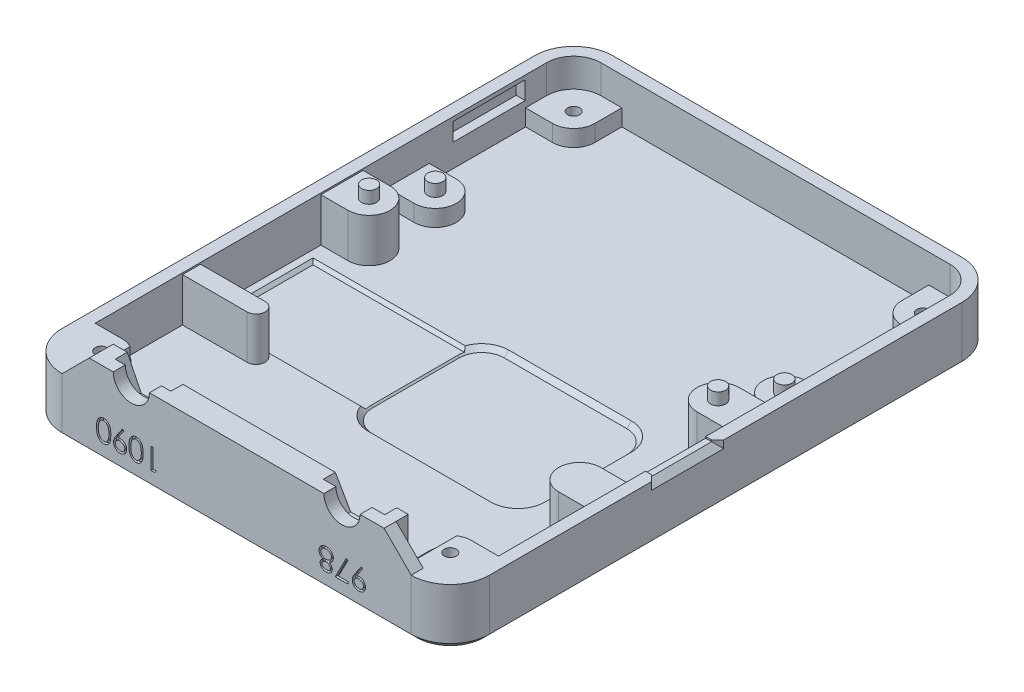
SolidWorks part; units mm, degrees
ref_plane "Front Plane" through (0, 0, 0) normal (0, 0, 1) x (1, 0, 0)
ref_plane "Top Plane" through (0, 0, 0) normal (0, 1, 0) x (1, 0, 0)
ref_plane "Right Plane" through (0, 0, 0) normal (1, 0, 0) x (0, 0, -1)
sketch "Sketch1" plane through (0, 0, 0) normal (0, 1, 0) x (1, 0, 0)
  line L0 (-33.8462, -25.5532) -> (31.1538, -25.5532)
  line L1 (-33.8462, 38.4468) -> (31.1538, 38.4468)
  line L2 (-33.8462, 38.4468) -> (-33.8462, 8.4468)
  line L3 (-33.8462, 8.4468) -> (31.1538, 8.4468)
  line L4 (31.1538, 38.4468) -> (31.1538, 8.4468)
  line L5 (-30.3462, 34.9468) -> (27.6538, 34.9468)
  line L6 (-30.3462, 34.9468) -> (-30.3462, 11.9468)
  line L7 (-30.3462, 11.9468) -> (27.6538, 11.9468)
  line L8 (27.6538, 34.9468) -> (27.6538, 11.9468)
  line L9 (-30.3462, 0.9468) -> (27.6538, 0.9468)
  line L10 (-30.3462, 0.9468) -> (-30.3462, -22.0532)
  line L11 (-33.8462, 4.4468) -> (31.1538, 4.4468)
  line L12 (-33.8462, 4.4468) -> (-33.8462, -25.5532)
  line L13 (-30.3462, -22.0532) -> (27.6538, -22.0532)
  line L14 (31.1538, 4.4468) -> (31.1538, -25.5532)
  line L15 (27.6538, 0.9468) -> (27.6538, -22.0532)
  line L16 (-37.9161, 25.3468) -> (-35.3276, 25.3468)
  line L17 (7.5538, 7.5472) -> (7.5538, 6.2645)
  line L18 (20.1538, 7.5472) -> (20.1538, 6.2645)
  dimension "D1" = 65
  dimension "D2" = 30
  dimension "D3" = 58
  dimension "D4" = 23
  dimension "D5" = 3.5
  dimension "D6" = 3.5
  dimension "D7" = 65
  dimension "D8" = 30
  dimension "D9" = 58
  dimension "D10" = 23
  dimension "D11" = 3.5
  dimension "D12" = 3.5
  dimension "D13" = 4
  dimension "D14" = 16.9
  dimension "D15" = 41.4
  dimension "D16" = 54
sketch "Sketch2" plane through (0, 0, 0) normal (0, 1, 0) x (1, 0, 0)
  line L0 (-33.8462, 38.4468) -> (-33.8462, 8.4468) construction
  line L1 (-30.3462, 39.4468) -> (27.6538, 39.4468)
  line L2 (-34.8462, 34.9468) -> (-34.8462, -43.5532)
  line L3 (-30.3462, -48.0532) -> (27.6538, -48.0532)
  line L4 (32.1538, 34.9468) -> (32.1538, -43.5532)
  line L5 (-33.8462, 38.4468) -> (31.1538, 38.4468) construction
  line L6 (31.1538, 38.4468) -> (31.1538, 8.4468) construction
  line L7 (-30.3462, 41.4468) -> (27.6538, 41.4468)
  line L8 (34.1538, 34.9468) -> (34.1538, -43.5532)
  line L9 (-30.3462, -50.0532) -> (27.6538, -50.0532)
  line L10 (-36.8462, 34.9468) -> (-36.8462, -43.5532)
  line L11 (-34.8462, 39.4468) -> (32.1538, 39.4468) construction
  line L12 (-34.8462, 39.4468) -> (-34.8462, -48.0532) construction
  line L13 (-36.8462, 41.4468) -> (-36.8462, -50.0532) construction
  line L14 (-36.8462, 41.4468) -> (34.1538, 41.4468) construction
  line L15 (32.1538, 39.4468) -> (32.1538, -48.0532) construction
  line L16 (34.1538, 41.4468) -> (34.1538, -50.0532) construction
  line L17 (-36.8462, -50.0532) -> (34.1538, -50.0532) construction
  line L18 (-34.8462, -48.0532) -> (32.1538, -48.0532) construction
  arc A0 (-30.3462, 39.4468) -> (-34.8462, 34.9468) centre (-30.3462, 34.9468) ccw
  arc A1 (-36.8462, 34.9468) -> (-30.3462, 41.4468) centre (-30.3462, 34.9468) cw
  arc A2 (32.1538, 34.9468) -> (27.6538, 39.4468) centre (27.6538, 34.9468) ccw
  arc A3 (34.1538, 34.9468) -> (27.6538, 41.4468) centre (27.6538, 34.9468) ccw
  arc A4 (27.6538, -50.0532) -> (34.1538, -43.5532) centre (27.6538, -43.5532) ccw
  arc A5 (-36.8462, -43.5532) -> (-30.3462, -50.0532) centre (-30.3462, -43.5532) ccw
  arc A6 (27.6538, -48.0532) -> (32.1538, -43.5532) centre (27.6538, -43.5532) ccw
  arc A7 (-30.3462, -48.0532) -> (-34.8462, -43.5532) centre (-30.3462, -43.5532) cw
  dimension "D6" = 4.5
  dimension "D7" = 6.5
  dimension "D8" = 4.5
  dimension "D9" = 6.5
  dimension "D10" = 6.5
  dimension "D11" = 4.5
  dimension "D1" = 1
  dimension "D2" = 1
  dimension "D3" = 1
  dimension "D4" = 87.5
  dimension "D5" = 2
extrude "Boss-Extrude1" add sketch "Sketch2" along normal blind 9.5
sketch "Sketch3" plane through (0, 0, 0) normal (0, 1, 0) x (1, 0, 0)
  line L0 (-30.3462, -48.0532) -> (27.6538, -48.0532)
  line L1 (-30.3462, 39.4468) -> (27.6538, 39.4468)
  line L2 (-34.8462, 34.9468) -> (-34.8462, -43.5532)
  line L4 (32.1538, 34.9468) -> (32.1538, -43.5532)
  arc A0 (-34.8462, -43.5532) -> (-30.3462, -48.0532) centre (-30.3462, -43.5532) ccw
  arc A1 (27.6538, -48.0532) -> (32.1538, -43.5532) centre (27.6538, -43.5532) ccw
  arc A2 (32.1538, 34.9468) -> (27.6538, 39.4468) centre (27.6538, 34.9468) ccw
  arc A3 (-30.3462, 39.4468) -> (-34.8462, 34.9468) centre (-30.3462, 34.9468) ccw
  point P15 (-34.8462, 39.4468)
  dimension "D1" = 4.5
  dimension "D2" = 4.5
  dimension "D3" = 87.5
extrude "Boss-Extrude2" add sketch "Sketch3" along normal blind 2
sketch "Sketch4" plane through (0, 2, 0) normal (0, 1, 0) x (1, 0, 0)
  line L1 (-4.1234, -3.5548) -> (16.2444, -3.5548)
  line L2 (-7.1234, -6.5548) -> (-7.1234, -20.9191)
  line L3 (-4.1234, -23.9191) -> (16.2444, -23.9191)
  line L4 (19.2444, -6.5548) -> (19.2444, -20.9191)
  arc A0 (16.2444, -23.9191) -> (19.2444, -20.9191) centre (16.2444, -20.9191) ccw
  arc A1 (-7.1234, -20.9191) -> (-4.1234, -23.9191) centre (-4.1234, -20.9191) ccw
  arc A2 (19.2444, -6.5548) -> (16.2444, -3.5548) centre (16.2444, -6.5548) ccw
  arc A3 (-7.1234, -6.5548) -> (-4.1234, -3.5548) centre (-4.1234, -6.5548) cw
  dimension "D1" = 3
extrude "Cut-Extrude2" cut sketch "Sketch4" against normal blind 0.75
chamfer "Chamfer1" distance 1.5 angle 45 8 edges at (6.0605, 2, 23.9191) (18.3657, 2, 23.0404) (-6.2447, 2, 23.0404) (19.2444, 2, 13.7369) (-7.1234, 2, 13.7369) (18.3657, 2, 4.4335) (-6.2447, 2, 4.4335) (6.0605, 2, 3.5548) tangent propagation no
sketch "Sketch5" plane through (0, 1.25, 0) normal (0, 1, 0) x (1, 0, 0)
  line L0 (-30.3462, 4.4468) -> (-34.8462, 4.4468)
  line L1 (-34.8462, 34.9468) -> (-34.8462, -43.5532) construction
  line L2 (-34.8462, 4.4468) -> (-34.8462, -2.5532)
  line L3 (-34.8462, -2.5532) -> (-30.3462, -2.5532)
  line L4 (27.6538, 4.4468) -> (32.1538, 4.4468)
  line L5 (32.1538, -43.5532) -> (32.1538, 34.9468) construction
  line L6 (32.1538, 4.4468) -> (32.1538, -2.5532)
  line L7 (32.1538, -43.5532) -> (32.1538, 34.9468) construction
  line L8 (32.1538, -2.5532) -> (27.6538, -2.5532)
  line L9 (32.1538, -18.5532) -> (32.1538, -25.5532)
  line L10 (-34.8462, -25.5532) -> (-24.1094, -25.5532)
  line L11 (-34.8462, -25.5532) -> (-34.8462, -22.5532)
  line L12 (-34.8462, -22.5532) -> (-24.1094, -22.5532)
  line L13 (32.1538, -25.5532) -> (27.6538, -25.5532)
  line L14 (27.6538, -18.5532) -> (32.1538, -18.5532)
  arc A0 (-30.3462, -2.5532) -> (-30.3462, 4.4468) centre (-30.3462, 0.9468) ccw
  arc A1 (27.6538, 4.4468) -> (27.6538, -2.5532) centre (27.6538, 0.9468) ccw
  arc A2 (-24.1094, -22.5532) -> (-24.1094, -25.5532) centre (-24.1094, -24.0532) cw
  arc A3 (27.6538, -18.5532) -> (27.6538, -25.5532) centre (27.6538, -22.0532) ccw
  dimension "D1" = 3
extrude "Boss-Extrude3" add sketch "Sketch5" along normal blind 8
sketch "Sketch6" plane through (0, 1.25, 0) normal (0, 1, 0) x (1, 0, 0)
  line L0 (-30.3462, 15.4468) -> (-34.8462, 15.4468)
  line L1 (-34.8462, 34.9468) -> (-34.8462, -43.5532) construction
  line L2 (-34.8462, 15.4468) -> (-34.8462, 8.4468)
  line L3 (-34.8462, 34.9468) -> (-34.8462, 4.4468) construction
  line L4 (-34.8462, 8.4468) -> (-30.3462, 8.4468)
  line L5 (-26.8462, 34.9468) -> (-26.8462, 39.4468)
  line L6 (27.6538, 39.4468) -> (-30.3462, 39.4468) construction
  line L7 (-26.8462, 39.4468) -> (-30.3462, 39.4468)
  line L8 (-30.3462, 31.4468) -> (-34.8462, 31.4468)
  line L9 (-34.8462, 31.4468) -> (-34.8462, 34.9468)
  line L10 (24.1538, 34.9468) -> (24.1538, 39.4468)
  line L11 (24.1538, 39.4468) -> (27.6538, 39.4468)
  line L12 (27.6538, 31.4468) -> (32.1538, 31.4468)
  line L13 (32.1538, 4.4468) -> (32.1538, 34.9468) construction
  line L14 (32.1538, 31.4468) -> (32.1538, 34.9468)
  line L15 (27.6538, 15.4468) -> (32.1538, 15.4468)
  line L16 (27.6538, 8.4468) -> (32.1538, 8.4468)
  line L17 (32.1538, -43.5532) -> (32.1538, 34.9468) construction
  line L18 (32.1538, 8.4468) -> (32.1538, 15.4468)
  arc A0 (-30.3462, 31.4468) -> (-26.8462, 34.9468) centre (-30.3462, 34.9468) ccw
  arc A1 (24.1538, 34.9468) -> (27.6538, 31.4468) centre (27.6538, 34.9468) ccw
  arc A2 (27.6538, 15.4468) -> (27.6538, 8.4468) centre (27.6538, 11.9468) ccw
  arc A3 (-30.3462, 8.4468) -> (-30.3462, 15.4468) centre (-30.3462, 11.9468) ccw
  arc A4 (-30.3462, 39.4468) -> (-34.8462, 34.9468) centre (-30.3462, 34.9468) ccw
  arc A5 (32.1538, 34.9468) -> (27.6538, 39.4468) centre (27.6538, 34.9468) ccw
  dimension "D1" = 4.5
  dimension "D2" = 4.5
extrude "Boss-Extrude4" add sketch "Sketch6" along normal blind 3.5
sketch "Sketch7" plane through (0, 0, 50.0532) normal (0, 0, 1) x (1, 0, 0)
  line L0 (27.6538, 9.5) -> (-30.3462, 9.5)
  line L3 (13.1538, 14) -> (-15.8462, 14)
  line L4 (-1.3462, 9.5) -> (-1.3462, 14) construction
  line L5 (-30.3462, 9.5) -> (27.6538, 9.5) construction
  line L6 (-30.3462, 9.5) -> (-25.8462, 14)
  line L7 (-25.8462, 14) -> (-21.8462, 14)
  line L9 (23.1538, 14) -> (19.1538, 14)
  line L13 (27.6538, 9.5) -> (23.1538, 14)
  arc A0 (-21.8462, 14) -> (-15.8462, 14) centre (-18.8462, 14) ccw
  arc A1 (13.1538, 14) -> (19.1538, 14) centre (16.1538, 14) ccw
  dimension "D2" = 35
  dimension "D1" = 4.5
  dimension "D6" = 3
  dimension "D7" = 3
  dimension "D3" = 4.5
  dimension "D4" = 45
  dimension "D5" = 4.5
extrude "Boss-Extrude5" add sketch "Sketch7" against normal up to vertex (2 mm away) up to point (-30.3462, 9.5, 48.0532)
sketch "Sketch10" plane through (0, 2, 0) normal (0, 1, 0) x (1, 0, 0)
  line L0 (-30.3462, -40.0532) -> (-34.8462, -40.0532)
  line L1 (27.6538, -40.0532) -> (32.1538, -40.0532)
  line L2 (-34.8462, -40.0532) -> (-34.8462, -43.5532)
  line L3 (-26.8462, -43.5532) -> (-26.8462, -48.0532)
  line L4 (32.1538, -43.5532) -> (32.1538, 34.9468) construction
  line L5 (-26.8462, -48.0532) -> (-30.3462, -48.0532)
  line L6 (32.1538, -40.0532) -> (32.1538, -43.5532)
  line L7 (24.1538, -43.5532) -> (24.1538, -48.0532)
  line L8 (-30.3462, -48.0532) -> (27.6538, -48.0532) construction
  line L9 (24.1538, -48.0532) -> (27.6538, -48.0532)
  arc A0 (-34.8462, -43.5532) -> (-30.3462, -48.0532) centre (-30.3462, -43.5532) ccw
  arc A1 (-26.8462, -43.5532) -> (-30.3462, -40.0532) centre (-30.3462, -43.5532) ccw
  arc A2 (32.1538, -43.5532) -> (27.6538, -48.0532) centre (27.6538, -43.5532) cw
  arc A3 (27.6538, -48.0532) -> (32.1538, -43.5532) centre (27.6538, -43.5532) ccw construction
  arc A4 (27.6538, -40.0532) -> (24.1538, -43.5532) centre (27.6538, -43.5532) ccw
extrude "Boss-Extrude6" add sketch "Sketch10" along normal up to vertex (7.5 mm away) up to point (-34.8462, 9.5, 43.5532)
sketch "Sketch11" plane through (34.1538, 0, 0) normal (1, 0, 0) x (0, 0, -1)
  line L1 (-15.6251, 10.2426) -> (-5.6251, 10.2426)
  line L2 (-15.6251, 10.2426) -> (-15.6251, 9.2424)
  line L3 (-15.6251, 9.2424) -> (-5.6251, 9.2424)
  line L4 (-5.6251, 10.2426) -> (-5.6251, 9.2424)
extrude "Cut-Extrude3" cut sketch "Sketch11" against normal up to next
chamfer "Chamfer2" distance 1 angle 45 3 edges at (34.1538, 9.3712, 5.6251) (34.1538, 9.3712, 15.6251) (34.1538, 9.2424, 10.6251)
sketch "Sketch12" plane through (-34.8462, 0, 0) normal (-1, 0, 0) x (0, 0, 1)
  line L1 (-31.3918, 8.8223) -> (-19.3918, 8.8223)
  line L2 (-31.3918, 8.8223) -> (-31.3918, 5.8223)
  line L3 (-31.3918, 5.8223) -> (-19.3918, 5.8223)
  line L4 (-19.3918, 8.8223) -> (-19.3918, 5.8223)
  line L5 (-31.3918, 8.8223) -> (-19.3918, 5.8223) construction
  line L6 (-31.3918, 5.8223) -> (-19.3918, 8.8223) construction
  point P0 (-25.3918, 7.3223)
  dimension "D1" = 12
  dimension "D2" = 3
chamfer "Chamfer4" distance 1 angle 45 8 edges at (34.1538, 0, 4.3032) (32.25, 0, -39.543) (32.25, 0, 48.1493) (-1.3462, 0, -41.4468) (-1.3462, 0, 50.0532) (-34.9423, 0, -39.543) (-34.9423, 0, 48.1493) (-36.8462, 0, 4.3032)
hole_wizard "Ø2.0 (2) Diameter Hole1" positions "Sketch14" profile "Sketch13" hole size "Ø2.0" standard "ANSI Metric" end condition through all
sketch "Sketch14" plane through (0, 0, 0) normal (0, -1, 0) x (-1, 0, 0)
  point P0 (30.3462, -43.5532)
sketch "Sketch13" plane through (-30.3462, 0, 43.5532) normal (1, 0, 0) x (0, 0, -1)
  line L0 (0, 0) -> (0, 14)
  line L1 (0, 14) -> (1, 14)
  line L2 (1, 14) -> (1, 0)
  line L5 (1, 0) -> (0, 0)
  line L11 (0, -6.35) -> (0, 107.95) construction
  dimension "Thru Hole Dia." = 2
  dimension "Thru Hole Depth" = 14
hole_wizard "Ø2.0 (2) Diameter Hole2" positions "Sketch16" profile "Sketch15" hole size "Ø2.0" standard "ANSI Metric" end condition through all
sketch "Sketch16" plane through (0, 0, 0) normal (0, -1, 0) x (-1, 0, 0)
  point P0 (-27.6538, -43.5532)
sketch "Sketch15" plane through (27.6538, 0, 43.5532) normal (1, 0, 0) x (0, 0, -1)
  line L0 (0, 0) -> (0, 14)
  line L1 (0, 14) -> (1, 14)
  line L2 (1, 14) -> (1, 0)
  line L5 (1, 0) -> (0, 0)
  line L11 (0, -6.35) -> (0, 107.95) construction
  dimension "Thru Hole Dia." = 2
  dimension "Thru Hole Depth" = 14
hole_wizard "Ø2.0 (2) Diameter Hole3" positions "Sketch18" profile "Sketch17" hole size "Ø2.0" standard "ANSI Metric" end condition through all
sketch "Sketch18" plane through (0, 0, 0) normal (0, -1, 0) x (-1, 0, 0)
  point P0 (30.3462, 34.9468)
sketch "Sketch17" plane through (-30.3462, 0, -34.9468) normal (1, 0, 0) x (0, 0, -1)
  line L0 (0, 0) -> (0, 14)
  line L1 (0, 14) -> (1, 14)
  line L2 (1, 14) -> (1, 0)
  line L5 (1, 0) -> (0, 0)
  line L11 (0, -6.35) -> (0, 107.95) construction
  dimension "Thru Hole Dia." = 2
  dimension "Thru Hole Depth" = 14
hole_wizard "Ø2.0 (2) Diameter Hole4" positions "Sketch20" profile "Sketch19" hole size "Ø2.0" standard "ANSI Metric" end condition through all
sketch "Sketch20" plane through (0, 0, 0) normal (0, -1, 0) x (-1, 0, 0)
  point P0 (-27.6538, 34.9468)
sketch "Sketch19" plane through (27.6538, 0, -34.9468) normal (1, 0, 0) x (0, 0, -1)
  line L0 (0, 0) -> (0, 14)
  line L1 (0, 14) -> (1, 14)
  line L2 (1, 14) -> (1, 0)
  line L5 (1, 0) -> (0, 0)
  line L11 (0, -6.35) -> (0, 107.95) construction
  dimension "Thru Hole Dia." = 2
  dimension "Thru Hole Depth" = 14
sketch "Sketch34" plane through (0, 2, 0) normal (0, 1, 0) x (1, 0, 0)
  line L1 (-5.843, -6.5548) -> (-32.1578, -6.5548)
  line L2 (-5.843, -6.5548) -> (-5.843, -20.9191)
  line L3 (-5.843, -20.9191) -> (-32.1578, -20.9191)
  line L4 (-32.1578, -6.5548) -> (-32.1578, -20.9191)
extrude "Cut-Extrude5" cut sketch "Sketch34" against normal blind 0.5
chamfer "Chamfer5" distance 1.5 angle 45 3 edges at (-20.3906, 2, 20.9191) (-32.1578, 2, 13.7369) (-20.3906, 2, 6.5548)
extrude "Cut-Extrude6" cut sketch "Sketch12" along normal blind 1.5
sketch "Sketch35" plane through (0, 9.5, 0) normal (0, 1, 0) x (1, 0, 0)
  line L0 (-30.3462, -48.0532) -> (-26.8462, -48.0532) construction
  line L1 (-28.5962, -48.0532) -> (25.7783, -48.0532)
  line L2 (-28.5962, -48.0532) -> (-28.5962, -29.9744)
  line L3 (-28.5962, -29.9744) -> (25.7783, -29.9744)
  line L4 (25.7783, -48.0532) -> (25.7783, -29.9744)
extrude "Cut-Extrude7" cut sketch "Sketch35" against normal blind 1.5
sketch "Sketch36" plane through (0, 0, 0) normal (0, -1, 0) x (1, 0, 0)
  line L0 (-5.6411, -4.4361) -> (-6.5788, -2.9987)
  line L1 (-5.6135, -17.5484) -> (-6.5451, -18.9896)
  line L2 (2.8733, -4.4181) -> (3.8048, -2.9769)
  line L3 (2.9009, -17.5304) -> (3.8385, -18.9678)
  line L4 (-14.7411, -31.67) -> (-15.5841, -32.9742)
  line L5 (-9.464, -23.5056) -> (-10.3585, -24.8894)
  line L6 (-9.5167, 1.5049) -> (-10.4169, 2.885)
  line L7 (-14.8281, 9.647) -> (-15.6766, 10.9477)
  line L8 (12.0008, 9.7035) -> (12.8438, 11.0078)
  line L9 (6.7238, 1.5391) -> (7.6182, 2.9229)
  line L10 (6.7764, -23.4714) -> (7.6767, -24.8515)
  line L11 (12.0878, -31.6135) -> (12.9363, -32.9142)
  line L12 (-3.5903, -40.4468) -> (-2.2438, -13.3244)
  line L13 (0.898, -40.4468) -> (-0.192, -13.3244)
  line L14 (-3.5903, -40.4468) -> (0.898, -40.4468)
  line L15 (-2.2438, -13.3244) -> (-0.192, -13.3244)
  arc A0 (12.9363, -32.9142) -> (12.8438, 11.0078) centre (-1.3701, -10.9832) ccw
  arc A1 (12.0878, -31.6135) -> (12.0008, 9.7035) centre (-1.3701, -10.9832) ccw
  arc A2 (2.9009, -17.5304) -> (2.8733, -4.4181) centre (-1.3701, -10.9832) ccw
  arc A3 (3.8385, -18.9678) -> (3.8048, -2.9769) centre (-1.3701, -10.9832) ccw
  arc A4 (7.6767, -24.8515) -> (7.6182, 2.9229) centre (-1.3701, -10.9832) ccw
  arc A5 (6.7764, -23.4714) -> (6.7238, 1.5391) centre (-1.3701, -10.9832) ccw
  arc A6 (-15.6766, 10.9477) -> (-15.5841, -32.9742) centre (-1.3701, -10.9832) ccw
  arc A7 (-14.8281, 9.647) -> (-14.7411, -31.67) centre (-1.3701, -10.9832) ccw
  arc A8 (-10.4169, 2.885) -> (-10.3585, -24.8894) centre (-1.3701, -10.9832) ccw
  arc A9 (-9.5167, 1.5049) -> (-9.464, -23.5056) centre (-1.3701, -10.9832) ccw
  arc A10 (-6.5788, -2.9987) -> (-6.5451, -18.9896) centre (-1.3701, -10.9832) ccw
  arc A11 (-5.6411, -4.4361) -> (-5.6135, -17.5484) centre (-1.3701, -10.9832) ccw
extrude "Cut-Extrude8" cut sketch "Sketch36" against normal blind 0.4
sketch "Sketch37" plane through (0, 0, 0) normal (0, 1, 0) x (1, 0, 0)
  line L0 (-1.9008, 5.7134) -> (12.3211, -8.0776)
  line L1 (12.3211, -8.0776) -> (16.1409, -4.1385)
  line L2 (16.1409, -4.1385) -> (3.4609, 11.2426)
  line L3 (3.4609, 11.2426) -> (9.8009, 20.3663)
  line L4 (9.8009, 20.3663) -> (15.1149, 16.2462)
  line L5 (15.1149, 16.2462) -> (17.8041, 19.0194)
  line L6 (17.8041, 19.0194) -> (12.774, 24.201)
  line L7 (12.774, 24.201) -> (13.7731, 25.4896)
  line L8 (13.7731, 25.4896) -> (13.4862, 25.712)
  line L9 (-1.9008, 5.7134) -> (-4.5225, 3.5521)
  line L10 (-4.5225, 3.5521) -> (-6.7547, 2.0307)
  line L11 (-6.7547, 2.0307) -> (-8.3897, 1.1526)
  line L12 (-8.3897, 1.1526) -> (-9.0215, 1.5916)
  line L13 (-9.0215, 1.5916) -> (-9.9767, 1.0787)
  line L14 (-9.9767, 1.0787) -> (-10.839, 0.7913)
  line L15 (-10.839, 0.7913) -> (-11.0799, 0.7913)
  line L16 (13.4862, 25.712) -> (-11.0799, 0.7913) construction
  line L17 (-11.0833, 1.0321) -> (-11.0799, 0.7913)
  line L18 (-10.8083, 1.8985) -> (-11.0833, 1.0321)
  line L19 (-10.3091, 2.8609) -> (-10.8083, 1.8985)
  line L20 (-10.7571, 3.4863) -> (-10.3091, 2.8609)
  line L21 (-9.9026, 5.1337) -> (-10.7571, 3.4863)
  line L22 (-8.4134, 7.3875) -> (-9.9026, 5.1337)
  line L23 (-6.2899, 10.0399) -> (-8.4134, 7.3875)
  line L24 (13.2596, 25.9958) -> (13.4862, 25.712)
  line L25 (11.9855, 24.9783) -> (13.2596, 25.9958)
  line L26 (6.7323, 29.9336) -> (11.9855, 24.9783)
  line L27 (3.9979, 27.2049) -> (6.7323, 29.9336)
  line L28 (8.1938, 21.9505) -> (3.9979, 27.2049)
  line L29 (-0.8381, 15.4803) -> (8.1938, 21.9505)
  line L30 (-16.3994, 27.9385) -> (-0.8381, 15.4803)
  line L31 (-20.2833, 24.0627) -> (-16.3994, 27.9385)
  line L32 (-6.2899, 10.0399) -> (-20.2833, 24.0627)
extrude "Cut-Extrude14" cut sketch "Sketch37" along normal blind 0.4
sketch "Sketch38" plane through (0, 0, 48.0532) normal (0, 0, -1) x (-1, 0, 0)
  line L0 (-23.1538, 14) -> (-21.2558, 14)
  line L1 (-23.1538, 14) -> (-23.1538, 8)
  line L2 (16.5875, 9.2512) -> (21.2063, 9.2512)
  line L3 (26.8462, 2) -> (-24.1538, 2) construction
  line L4 (-21.2558, 14) -> (-18.7048, 9.5816)
  line L5 (-18.7048, 9.5816) -> (-13.6029, 9.5816)
  line L6 (-13.6029, 9.5816) -> (-11.0519, 14)
  line L7 (-23.9027, 2) -> (-9.4512, 2)
  line L8 (21.2063, 9.2512) -> (23.5157, 14)
  line L9 (-19.9803, 16.2092) -> (-21.135, 14.2092) [skipped]
  line L10 (-14.8081, 18.4184) -> (-17.1175, 18.4184) [skipped]
  line L11 (-12.3274, 16.2092) -> (-13.4821, 18.2092) [skipped]
  line L12 (14.2781, 14) -> (16.5875, 9.2512)
  line L14 (25.6503, 14) -> (23.5157, 14)
  line L16 (-9.4512, 14) -> (12.1436, 14)
  line L18 (14.2781, 14) -> (12.1436, 14)
  line L19 (-24.1538, 8) -> (-23.1538, 8)
  line L20 (-9.4512, 14) -> (-11.0519, 14)
  line L22 (-24.1538, 8) -> (-24.1538, 2)
  line L23 (-24.1538, 2) -> (-23.9027, 2)
  line L24 (25.6503, 14) -> (25.8462, 14)
  line L25 (25.8462, 14) -> (25.8462, 8)
  line L26 (25.8462, 8) -> (26.8462, 8)
  line L27 (26.8462, 8) -> (26.8462, 2)
  line L28 (26.8462, 2) -> (-9.4512, 2)
  arc A0 (15.4328, 11.2512) -> (22.361, 11.2512) centre (18.8969, 13.2512) ccw construction
  arc A2 (-19.6687, 11.2512) -> (-12.639, 11.2512) centre (-16.1538, 14) ccw construction
extrude "Boss-Extrude7" add sketch "Sketch38" along normal blind 2
sketch "Sketch39" plane through (0, 0, 50.0532) normal (0, 0, 1) x (1, 0, 0)
  line L0 (-25.8321, 6.4571) -> (-13.0275, 6.4571) construction
  line L1 (9.3531, 6.4571) -> (23.0562, 6.4571) construction
  text T0 "1090"
  text T1 "978"
extrude "Cut-Extrude15" cut sketch "Sketch39" against normal blind 0.5
sketch "Sketch40" plane through (0, 4.75, 0) normal (0, 1, 0) x (1, 0, 0)
  circle A0 centre (-30.3462, 11.9468) radius 1.25
  circle A1 centre (27.6538, 11.9468) radius 1.25
  dimension "D1" = 2.5
  dimension "D2" = 2.5
extrude "Boss-Extrude8" add sketch "Sketch40" along normal blind 2
sketch "Sketch41" plane through (0, 9.25, 0) normal (0, 1, 0) x (1, 0, 0)
  circle A0 centre (-30.3462, 0.9468) radius 1.25
  circle A2 centre (27.6538, 0.9468) radius 1.25
  dimension "D1" = 2.5
  dimension "D2" = 2.5
extrude "Boss-Extrude9" add sketch "Sketch41" along normal blind 2
